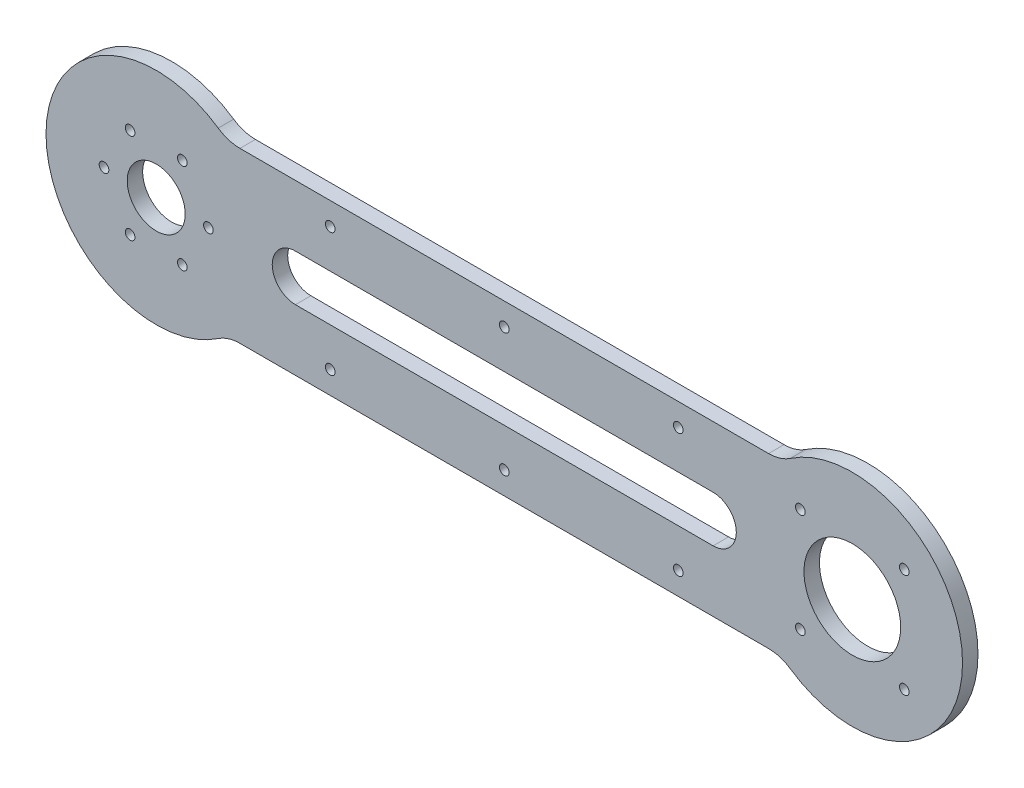
SolidWorks part; units mm, degrees
material "AISI 304"
ref_plane "前视基准面" through (0, 0, 0) normal (0, 0, 1) x (1, 0, 0)
ref_plane "上视基准面" through (0, 0, 0) normal (0, 1, 0) x (1, 0, 0)
ref_plane "右视基准面" through (0, 0, 0) normal (1, 0, 0) x (0, 0, -1)
other "Configuration Table"
sketch "草图1" plane through (0, 0, 0) normal (0, 0, 1) x (1, 0, 0)
  line L0 (0, 0) -> (75.8278, 90.3681) construction
  line L1 (-41.2921, 0) -> (234.2847, 0) construction
  line L2 (18.3194, 21.8323) -> (161.6806, 21.8323)
  line L3 (18.3194, -21.8323) -> (161.6806, -21.8323)
  arc A0 (18.3194, 21.8323) -> (18.3194, -21.8323) centre (0, 0) ccw
  arc A1 (161.6806, -21.8323) -> (161.6806, 21.8323) centre (180, 0) ccw
  dimension "D1" = 57
  dimension "D2" = 57
  dimension "D3" = 180
  dimension "D4" = 50
extrude "凸台-拉伸1" add sketch "草图1" along normal blind 4
fillet "圆角1" radius 10 4 edges at (161.6806, 21.8323, 2) (161.6806, -21.8323, 2) (18.3194, -21.8323, 2) (18.3194, 21.8323, 2)
sketch "草图2" plane through (0, 0, 4) normal (0, 0, 1) x (1, 0, 0)
  circle A0 centre (0, 0) radius 7.5
  circle A1 centre (-13.5, 0) radius 1.25
  dimension "D1" = 15
  dimension "D2" = 2.5
  dimension "D3" = 13.5
extrude "切除-拉伸1" cut sketch "草图2" against normal blind 5
pattern_circular "阵列(圆周)1" count 6 over 360 about axis through (0, 0, 4) along (0, 0, 1) of "切除-拉伸1"
sketch "草图3" plane through (0, 0, 4) normal (0, 0, 1) x (1, 0, 0)
  line L0 (-42.8634, 0) -> (245.614, 0) construction
  line L1 (180, 28.5) -> (180, -39.8135) construction
  line L2 (180, 0) -> (241.1851, 61.1851) construction
  arc A0 (163.9694, -23.5641) -> (163.9694, 23.5641) centre (180, 0) ccw construction
  circle A1 centre (180, 0) radius 12.5
  circle A2 centre (193.435, 13.435) radius 1.25
  dimension "D1" = 25
  dimension "D3" = 2.5
  dimension "D2" = 45
  dimension "D4" = 19
extrude "切除-拉伸2" cut sketch "草图3" against normal blind 5
pattern_circular "阵列(圆周)2" count 4 over 360 about axis through (180, 0, 4) along (0, 0, 1) of "切除-拉伸2"
sketch "草图4" plane through (0, 0, 4) normal (0, 0, 1) x (1, 0, 0)
  line L0 (0, 0) -> (223.7734, 0) construction
  line L1 (30, -6) -> (30, 6)
  line L2 (30, 6) -> (150, 6)
  line L3 (150, 6) -> (150, -6)
  line L4 (180, 28.5) -> (180, -31.6233) construction
  line L5 (30, -6) -> (150, -6)
  arc A0 (163.9694, -23.5641) -> (163.9694, 23.5641) centre (180, 0) ccw construction
  point P14 (150, 0)
  point P15 (30, 0)
  dimension "D1" = 30
  dimension "D2" = 30
  dimension "D3" = 6
extrude "切除-拉伸3" cut sketch "草图4" against normal blind 5
fillet "圆角2" 2 edges at (30, 6, 2) (30, -6, 2) type full round first side face at (90, 6, 2) second side face at (90, -6, 2) middle face at (30, 0, 2)
fillet "圆角3" 2 edges at (150, 6, 2) (150, -6, 2) type full round first side face at (93, 6, 2) second side face at (93, -6, 2) middle face at (150, 0, 2)
sketch "草图5" plane through (0, 0, 4) normal (0, 0, 1) x (1, 0, 0)
  line L0 (-38.01, 0) -> (223.9251, 0) construction
  circle A0 centre (45, 16) radius 1.25
  circle A1 centre (45, -16) radius 1.25
  dimension "D2" = 2.5
  dimension "D1" = 45
  dimension "D3" = 16
extrude "切除-拉伸5" cut sketch "草图5" against normal blind 5
pattern_linear "阵列(线性)2" count 3 spacing 45 along (1, 0, 0) of "切除-拉伸5"
